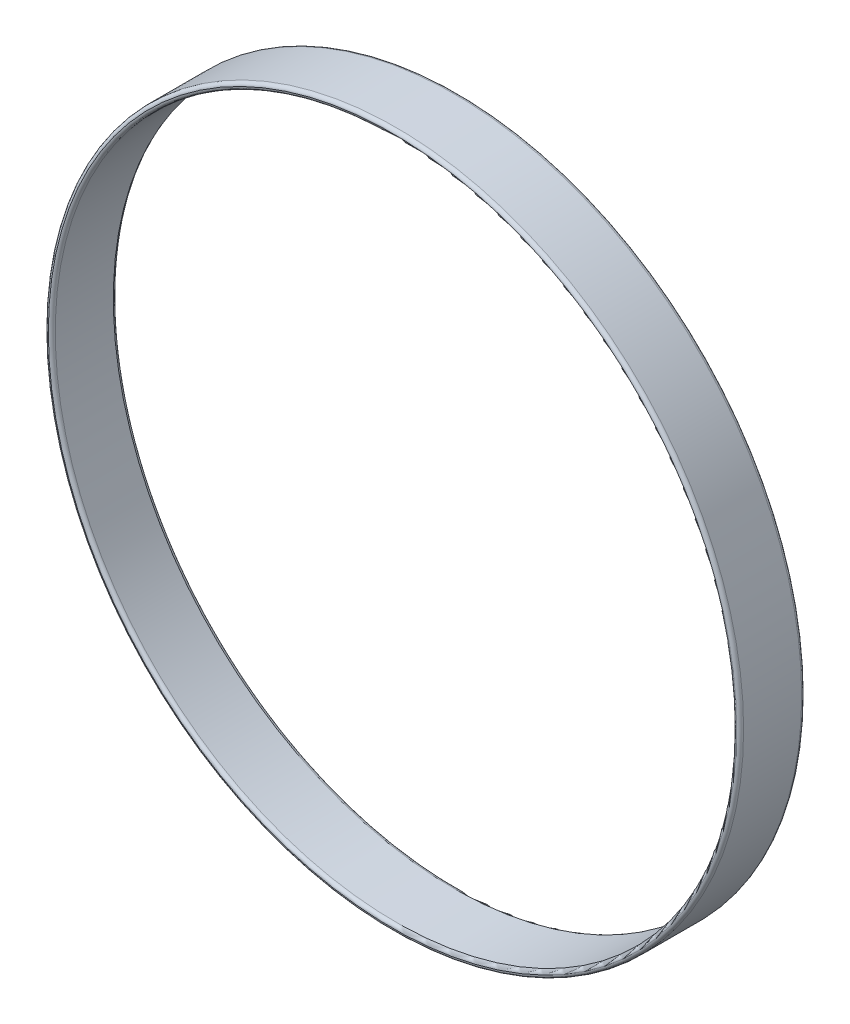
SolidWorks part; units mm, degrees
ref_plane "Plan de face" through (0, 0, 0) normal (0, 0, 1) x (1, 0, 0)
ref_plane "Plan de dessus" through (0, 0, 0) normal (0, 1, 0) x (1, 0, 0)
ref_plane "Plan de droite" through (0, 0, 0) normal (1, 0, 0) x (0, 0, -1)
sketch "Esquisse1" plane through (0, 0, 0) normal (0, 0, 1) x (1, 0, 0)
  circle A0 centre (0, 0) radius 50
  dimension "D1" = 100
extrude "Boss.-Extru.1" add sketch "Esquisse1" along normal blind 9.35
shell "Coque1" thickness 1 removed face at (50, 0, 9.35) removed face at (50, 0, 0)
fillet "Congé1" radius 0.5 4 edges at (50, 0, 0) (49, 0, 0) (50, 0, 9.35) (49, 0, 9.35)
